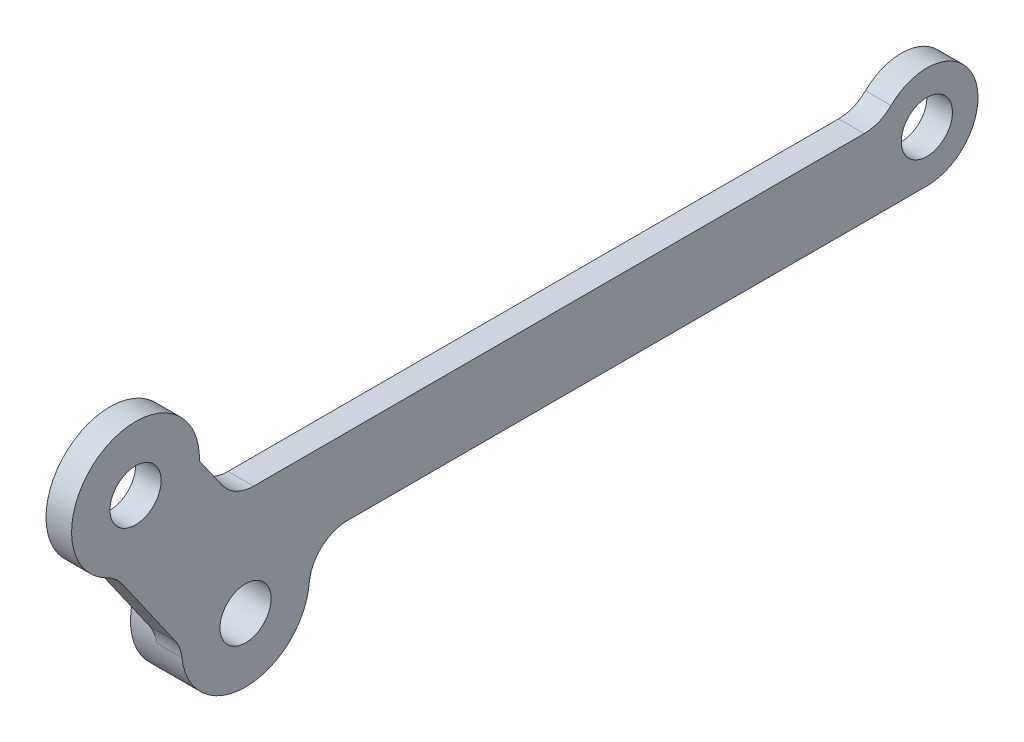
SolidWorks part; units mm, degrees
ref_plane "前视基准面" through (0, 0, 0) normal (0, 0, 1) x (1, 0, 0)
ref_plane "上视基准面" through (0, 0, 0) normal (0, 1, 0) x (1, 0, 0)
ref_plane "右视基准面" through (0, 0, 0) normal (1, 0, 0) x (0, 0, -1)
other "Configuration Table"
sketch "草图1" plane through (0, 0, 0) normal (1, 0, 0) x (0, 0, -1)
  line L1 (0, 0) -> (54.2012, 0)
  line L2 (0, 0) -> (4.2012, -6)
  line L3 (4.2012, -6) -> (54.2012, -6)
  line L4 (54.2012, 0) -> (54.2012, -6)
  line L5 (-10.9556, 1.6987) -> (-4.4024, 6.2873)
  line L6 (-10.9556, 1.6987) -> (-2.352, -10.5886)
  line L7 (-2.352, -10.5886) -> (4.2012, -6)
  line L8 (-4.4024, 6.2873) -> (4.2012, -6)
  circle A0 centre (-7.679, 3.993) radius 5
  circle A1 centre (0.9246, -8.2943) radius 5
  circle A3 centre (54.2012, -2) radius 4
  circle A4 centre (-7.679, 3.993) radius 2
  circle A5 centre (54.2012, -2) radius 2
  circle A6 centre (0.9246, -8.2943) radius 2
  dimension "D5" = 10
  dimension "D6" = 10
  dimension "D8" = 8
  dimension "D9" = 4
  dimension "D1" = 125
  dimension "D2" = 50
  dimension "D3" = 6
  dimension "D4" = 8
  dimension "D7" = 15
extrude "凸台-拉伸1" add sketch "草图1" along normal blind 2 contours A3 L1 L2 A1 L3 | A0 | L8 L5 L6 L7 | A1 | A3 region at (0, -2.9623, -26.6419)
extrude "凸台-拉伸2" add sketch "草图1<4>" against normal blind 2 contours A1
sketch "草图1<4>" plane through (0, 0, 0) normal (1, 0, 0) x (0, 0, -1) same geometry as "草图1"
extrude "切除-拉伸1" cut sketch "草图1<3>" along normal through all both and the other way through all contours A4 | A6 | A5
sketch "草图1<3>" plane through (0, 0, 0) normal (1, 0, 0) x (0, 0, -1) same geometry as "草图1"
fillet "圆角1" radius 3 5 edges at (1, 0, -50.7371) (1, -8.1312, 4.0727) (1, -0.7588, 9.2349) (1, -6, -5.3672) (1, 0, 0)
